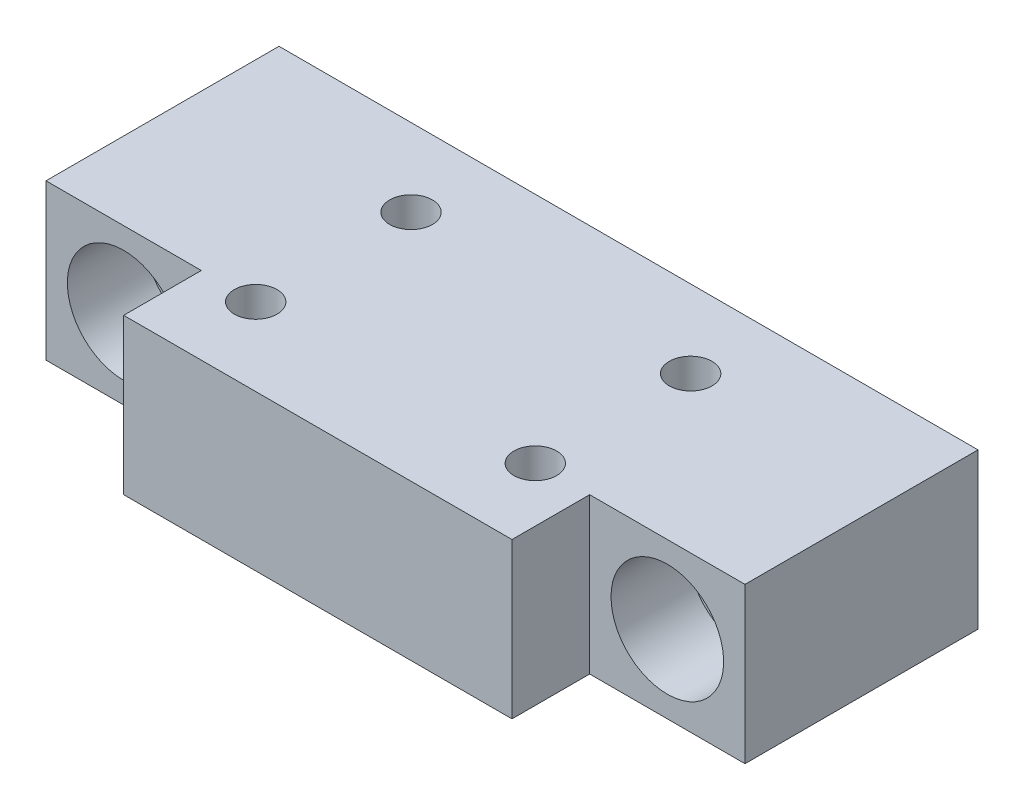
SolidWorks part; units mm, degrees
ref_plane "Front Plane" through (0, 0, 0) normal (0, 0, 1) x (1, 0, 0)
ref_plane "Top Plane" through (0, 0, 0) normal (0, 1, 0) x (1, 0, 0)
ref_plane "Right Plane" through (0, 0, 0) normal (1, 0, 0) x (0, 0, -1)
sketch "Sketch1" plane through (0, 0, 0) normal (0, 1, 0) x (1, 0, 0)
  line L0 (-45, 40) -> (45, 40)
  line L2 (-25, 10) -> (-45, 10)
  line L4 (-45, 10) -> (-45, 40)
  line L5 (-25, 0) -> (-25, 10)
  line L7 (25, 0) -> (-25, 0)
  line L8 (0, -1000) -> (0, 49000) construction
  line L9 (25, 0) -> (25, 10)
  line L10 (45, 10) -> (45, 40)
  line L12 (25, 10) -> (45, 10)
  point P2 (-45, -5)
  point P3 (0, 0)
  point P8 (0, 0)
  point P13 (0, 0)
  point P18 (0, 40)
  dimension "D1" = 40
  dimension "D2" = 50
  dimension "D3" = 20
  dimension "D4" = 30
  dimension "D5" = 90
extrude "Body" add sketch "Sketch1" along normal mid plane 20
sketch "Sketch2" plane through (0, 0, -10) normal (0, 0, 1) x (1, 0, 0)
  line L1 (-25, 10) -> (-25, -10) construction
  circle A0 centre (-35, 0) radius 7.25
  dimension "D1" = 14.5
  dimension "D2" = 10
extrude "Spring_Hole" cut sketch "Sketch2" against normal blind 10
sketch "Sketch3" plane through (0, 0, -20) normal (0, 0, 1) x (1, 0, 0)
  circle A0 centre (-35, 0) radius 3.25
  dimension "D1" = 6.5
extrude "Shaft_Hole" cut sketch "Sketch3" against normal through all and the other way through all
sketch "Sketch4" plane through (0, 10, 0) normal (0, 1, 0) x (1, 0, 0)
  line L0 (45, 40) -> (-45, 40) construction
  circle A0 centre (-18, 10) radius 2.75
  circle A1 centre (-18, 30) radius 2.75
  point P7 (0, 0)
  dimension "D1" = 5.5
  dimension "D2" = 18
  dimension "D3" = 10
  dimension "D4" = 10
extrude "Fixation_Hole" cut sketch "Sketch4" along normal through all from surface starting at face at (0, -10, -15)
mirror "Mirror1" about plane through (0, 0, 0) normal (1, 0, 0) of "Spring_Hole", "Fixation_Hole", "Shaft_Hole"
sketch "Sketch7" plane through (0, 0, -40) normal (0, 0, -1) x (-1, 0, 0)
  line L0 (0, -1000) -> (0, 49000) construction
  circle A0 centre (-10, 0) radius 3.2
  circle A1 centre (10, 0) radius 3.2
  dimension "D1" = 6.4
  dimension "D2" = 10
extrude "Inserts_Top" cut sketch "Sketch7" against normal blind 9.5
sketch "Sketch8" plane through (0, -10, 0) normal (0, -1, 0) x (1, 0, 0)
  circle A0 centre (-18, -10) radius 4.5
  circle A1 centre (18, -10) radius 4.5
  circle A2 centre (-18, -30) radius 4.5
  circle A3 centre (18, -30) radius 4.5
  dimension "D1" = 9
extrude "M5_Screw_Place" cut sketch "Sketch8" against normal blind 5
sketch "Sketch9" plane through (0, 0, -40) normal (0, 0, -1) x (-1, 0, 0)
  circle A0 centre (-35, 0) radius 6.2
  dimension "D1" = 12.4
extrude "Linear_Bearing_Place" cut sketch "Sketch9" against normal blind 19
mirror "Mirror2" about plane through (0, 0, 0) normal (1, 0, 0) of "Linear_Bearing_Place"
